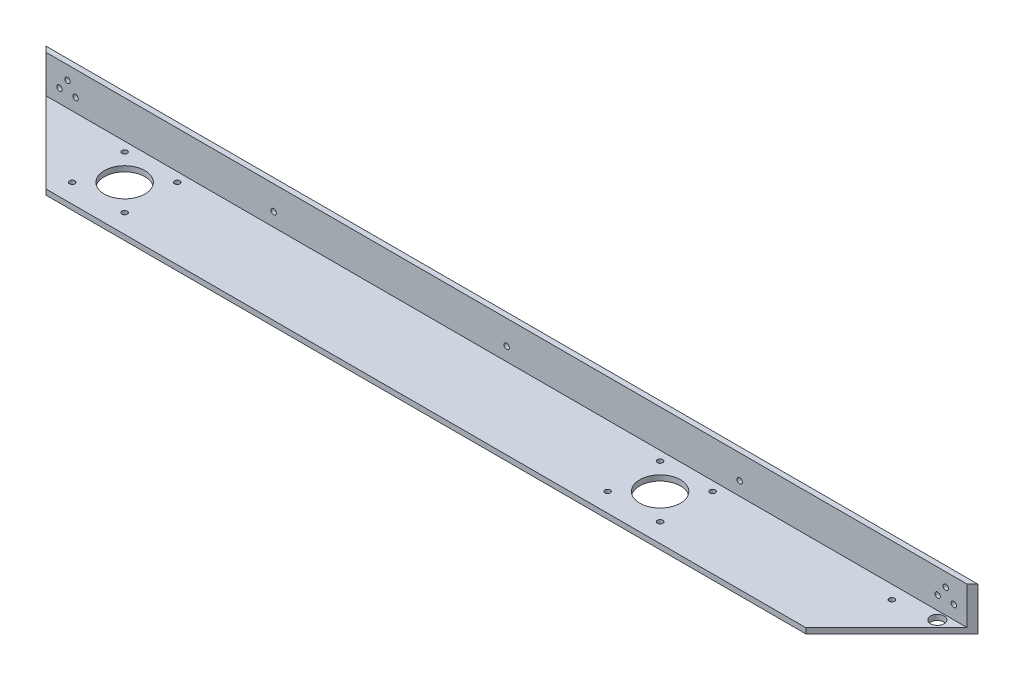
SolidWorks part; units mm, degrees
ref_plane "Front Plane" through (0, 0, 0) normal (0, 0, 1) x (1, 0, 0)
ref_plane "Top Plane" through (0, 0, 0) normal (0, 1, 0) x (1, 0, 0)
ref_plane "Right Plane" through (0, 0, 0) normal (1, 0, 0) x (0, 0, -1)
sketch "Sketch1" plane through (0, 0, 0) normal (1, 0, 0) x (0, 0, -1)
  line L0 (0, 0) -> (-50.8, 0)
  line L1 (-50.8, 0) -> (-50.8, 3.175)
  line L2 (-50.8, 3.175) -> (-3.175, 3.175)
  line L3 (-3.175, 3.175) -> (-3.175, 25.4)
  line L4 (-3.175, 25.4) -> (0, 25.4)
  line L5 (0, 25.4) -> (0, 0)
  dimension "LHeight" = 25.4
  dimension "LWidth" = 50.8
  dimension "LMaterialThickness" = 3.175
  dimension "D1" = 47.625
  dimension "D2" = 22.225
  dimension "D3" = 3.175
extrude "Boss-Extrude1" add sketch "Sketch1" along normal blind 550
chamfer "Chamfer7" distance 50.8 angle 45 1 edges at (0, 1.5875, 50.8)
chamfer "Chamfer8" distance 50.8 angle 45 1 edges at (550, 1.5875, 50.8)
sketch "BotthomHoles-Sketch2" plane through (0, 3.175, 0) normal (0, 1, 0) x (1, 0, 0)
  line L0 (546.825, -3.175) -> (3.175, -3.175) construction
  line L1 (550, 0) -> (0, 0) construction
  line L2 (499.2, -50.8) -> (50.8, -50.8) construction
  circle A0 centre (70.575, -24.175) radius 12
  circle A1 centre (386.575, -24.175) radius 12
  circle A2 centre (55.075, -8.675) radius 1.5875
  circle A3 centre (86.075, -8.675) radius 1.5875
  circle A4 centre (371.075, -8.675) radius 1.5875
  circle A5 centre (402.075, -8.675) radius 1.5875
  circle A6 centre (55.075, -39.675) radius 1.5875
  circle A7 centre (86.075, -39.675) radius 1.5875
  circle A8 centre (371.075, -39.675) radius 1.5875
  circle A9 centre (402.075, -39.675) radius 1.5875
  circle A11 centre (510.3125, -11.1125) radius 1.5875
  circle A12 centre (534, -8) radius 4
  point P30 (541.4309, -1.646)
  dimension "D9" = 3.175
  dimension "D10" = 24
  dimension "D14" = 8
  dimension "D2" = 8.675
  dimension "D3" = 31
  dimension "D4" = 15.5
  dimension "D5" = 15.5
  dimension "D6" = 31
  dimension "D7" = 15.5
  dimension "D8" = 31
  dimension "D11" = 21
  dimension "D12" = 316
  dimension "D13" = 70.575
  dimension "D17" = 39.6875
  dimension "D15" = 16
  dimension "D16" = 8
  dimension "D18" = 39.6875
extrude "BottomHoles-Cut-Extrude1" cut sketch "BotthomHoles-Sketch2" against normal through all
sketch "LeftSideHoles-Sketch3" plane through (0, 0, 0) normal (0, 0, -1) x (-1, 0, 0)
  line L0 (0, 0) -> (0, 25.4) construction
  line L1 (-550, 0) -> (-550, 25.4) construction
  line L2 (-550, 25.4) -> (0, 25.4) construction
  circle A1 centre (-534.125, 17.4625) radius 1.5875
  circle A2 centre (-538.8875, 11.1125) radius 1.5875
  circle A3 centre (-529.3625, 11.1125) radius 1.5875
  circle A4 centre (-11.1125, 11.1125) radius 1.5875
  circle A5 centre (-20.6375, 11.1125) radius 1.5875
  circle A6 centre (-15.875, 17.4625) radius 1.5875
  circle A8 centre (-412.5, 11.1125) radius 1.5875
  circle A9 centre (-275, 11.1125) radius 1.5875
  circle A10 centre (-137.5, 11.1125) radius 1.5875
  dimension "D7" = 3.175
  dimension "D2" = 15.875
  dimension "D4" = 11.1125
  dimension "D6" = 15.875
  dimension "D8" = 137.5
  dimension "D9" = 137.5
  dimension "D10" = 137.5
  dimension "D5" = 11.1125
  dimension "D11" = 11.1125
  dimension "D3" = 7.9375
  dimension "D12" = 20.6375
  dimension "D13" = 20.6375
extrude "LeftSideHoles-Cut-Extrude2" cut sketch "LeftSideHoles-Sketch3" against normal through all
equation "\"LowerRailWidth\"= 2.00in"
equation "\"LowerRailHeight\"= 1.00in"
equation "\"RailThickness\"= .125in'Spec"
equation "\"SideRailHoleY1FromEdge\"= \"HoleOffsetFromEdge\""
equation "\"SideRailHoleX1FromSide\"= \"HoleOffsetFromSide\""
equation "\"StepperHoleDiameter\"= 24mm"
equation "\"StepperMountingHoleDiameter\"= 3.175mm"
equation "\"SideRailLength\"= 550mm"
equation "\"StepperMountingHoleDistance\"= 31mm'Spec"
equation "\"VSWidth\"= 1.25in'Spec"
equation "\"StepperMountingHoleOffsetFromLeftOrRightSide\"= \"StepperMountingHoleOffsetFromItsSide\" + \"RailThickness\""
equation "\"HoleOffsetFromEdge\"= \"RailThickness\" * 2.5"
equation "\"HoleOffsetFromSide\"= \"RailThickness\" * 3.5"
equation "\"StepperMountingHoleOffsetFromItsSide\"= 5.5mm'Spec"
equation "\"SideRailHoleX2FromSide\"= \"VSWidth\" - \"HoleOffsetFromEdge\" - \"RailThickness\"'Equals 20.6375"
equation "\"FasteningHoleDiameter\"= .125in"
equation "\"SideRailHoleY2FromSide\"= \"HoleOffsetFromSide\""
equation "\"LHeight@Sketch1\"=\"LowerRailHeight\""
equation "\"LWidth@Sketch1\"=\"LowerRailWidth\""
equation "\"D1@Chamfer7\"=\"LowerRailWidth\""
equation "\"D1@Chamfer8\"=\"LowerRailWidth\""
equation "\"D2@BotthomHoles-Sketch2\" = \"StepperMountingHoleOffsetFromLeftOrRightSide\""
equation "\"D3@BotthomHoles-Sketch2\" = \"StepperMountingHoleDistance\""
equation "\"D4@BotthomHoles-Sketch2\" = \"StepperMountingHoleDistance\" / 2"
equation "\"D5@BotthomHoles-Sketch2\"= \"StepperMountingHoleDistance\" / 2"
equation "\"D6@BotthomHoles-Sketch2\" = \"StepperMountingHoleDistance\""
equation "\"D7@BotthomHoles-Sketch2\" = \"StepperMountingHoleDistance\" / 2"
equation "\"D8@BotthomHoles-Sketch2\" = \"StepperMountingHoleDistance\""
equation "\"D9@BotthomHoles-Sketch2\" = \"StepperMountingHoleDiameter\""
equation "\"D10@BotthomHoles-Sketch2\" = \"StepperHoleDiameter\""
equation "\"D2@LeftSideHoles-Sketch3\"=\"VSMidSideRailHoleXFromSideToCenter\" - \"RailThickness\""
equation "\"D4@LeftSideHoles-Sketch3\" = \"SideRailHoleY2FromSide\""
equation "\"D7@LeftSideHoles-Sketch3\" = \"FasteningHoleDiameter\""
equation "\"D1@Boss-Extrude1\"=\"SideRailLength\""
equation "\"D6@LeftSideHoles-Sketch3\"=\"VSMidSideRailHoleXFromSideToCenter\" - \"RailThickness\""
equation "\"DistanceBetweenFrontToBackStepperHoles\"= \"BedLength\" - \"DistanceFromBedFrontToFirstLeftStepperHole\"'Equals 316"
equation "\"BedThirdSize\"= 70mm"
equation "\"BedLWidth\"= \"BedThirdSize\"'Equals 70"
equation "\"BedInnerSquareWidth\"= \"BedThirdSize\" * 3'Equals 210"
equation "\"BedInnerSquareLength\"= \"BedInnerSquareWidth\""
equation "\"BedLength\"= \"BedInnerSquareLength\" + \"BedLWidth\" * 2 + \"BedIncreasedByLength\"'Equals 350"
equation "\"D12@BotthomHoles-Sketch2\"=\"DistanceBetweenFrontToBackStepperHoles\""
equation "\"DistanceFromFrontSideToFirstLeftStepperHole\"= \"DistanceFromFrontSideToBedFront\" + \"DistanceFromBedFrontToFirstLeftStepperHole\"'Equals 70.575"
equation "\"D13@BotthomHoles-Sketch2\"=\"DistanceFromFrontSideToFirstLeftStepperHole\""
equation "\"DistanceFromBedFrontToFirstLeftStepperHole\"= \"LeadScrewNutPadSize\" + 10mm'Equals 34"
equation "\"DistanceFromFrontSideToBedFront\"= \"RailThickness\" + \"BeltTensionerDepth\" + 10mm'Equals 36.575"
equation "\"BeltTensionerDepth\"= \"BeltTensionerBackWallThickness\" + \"BeltTensionerInnerDepth\"'Equals 23.4"
equation "\"BeltTensionerBackWallThickness\"= 4mm"
equation "\"20TGT2PulleyDiameter\"= 17.9mm'Spec"
equation "\"BeltTensionerSpaceBetweenPulleyAndWall\"= 1.5mm"
equation "\"BeltTensionerInnerDepth\"= \"20TGT2PulleyDiameter\" + \"BeltTensionerSpaceBetweenPulleyAndWall\""
equation "\"BedIncreasedByLength\"= 0mm"
equation "\"LowerCornerBlockWidth\"= \"LowerRailWidth\" - \"RailThickness\" * 2'Room for left front stepper"
equation "\"D17@BotthomHoles-Sketch2\"=\"CornerEnclosureOffset\""
equation "\"CornerEnclosureOffset\"= \"LowerCornerBlockWidth\" - \"HoleOffsetFromEdge\" + \"RailThickness\""
equation "\"LeadScrewNutMountingHoleFlangeDiameter\"= 22mm'Spec"
equation "\"LeadScrewNutPadSize\"= \"LeadScrewNutMountingHoleFlangeDiameter\" + 2mm'Equals 24"
equation "\"LeftOrRightEnclosureOffsets\"= \"SideRailLength\" / 4"
equation "\"D8@LeftSideHoles-Sketch3\"=\"LeftOrRightEnclosureOffsets\""
equation "\"D9@LeftSideHoles-Sketch3\"=\"LeftOrRightEnclosureOffsets\""
equation "\"D10@LeftSideHoles-Sketch3\"=\"LeftOrRightEnclosureOffsets\""
equation "\"D5@LeftSideHoles-Sketch3\"=\"SideRailHoleX1FromSide\""
equation "\"D11@LeftSideHoles-Sketch3\"=\"SideRailHoleX1FromSide\""
equation "\"D3@LeftSideHoles-Sketch3\"=\"SideRailHoleY1FromEdge\""
equation "\"VSMidSideRailHoleXFromSideToCenter\"= \"RailThickness\" * 6"
equation "\"D12@LeftSideHoles-Sketch3\"=\"SideRailHoleX2FromSide\""
equation "\"D13@LeftSideHoles-Sketch3\"=\"SideRailHoleX2FromSide\""
equation "\"LowerRailCableHoleDiameter\"= 8mm"
equation "\"LowerRailCableHoleOffsetFromSide\"= 8mm"
equation "\"LowerRailCableHoleXOffsetFromEdge\" = 16mm"
equation "\"D15@BotthomHoles-Sketch2\"=\"LowerRailCableHoleXOffsetFromEdge\""
equation "\"D16@BotthomHoles-Sketch2\"=\"LowerRailCableHoleOffsetFromSide\""
equation "\"D14@BotthomHoles-Sketch2\"=\"LowerRailCableHoleDiameter\""
